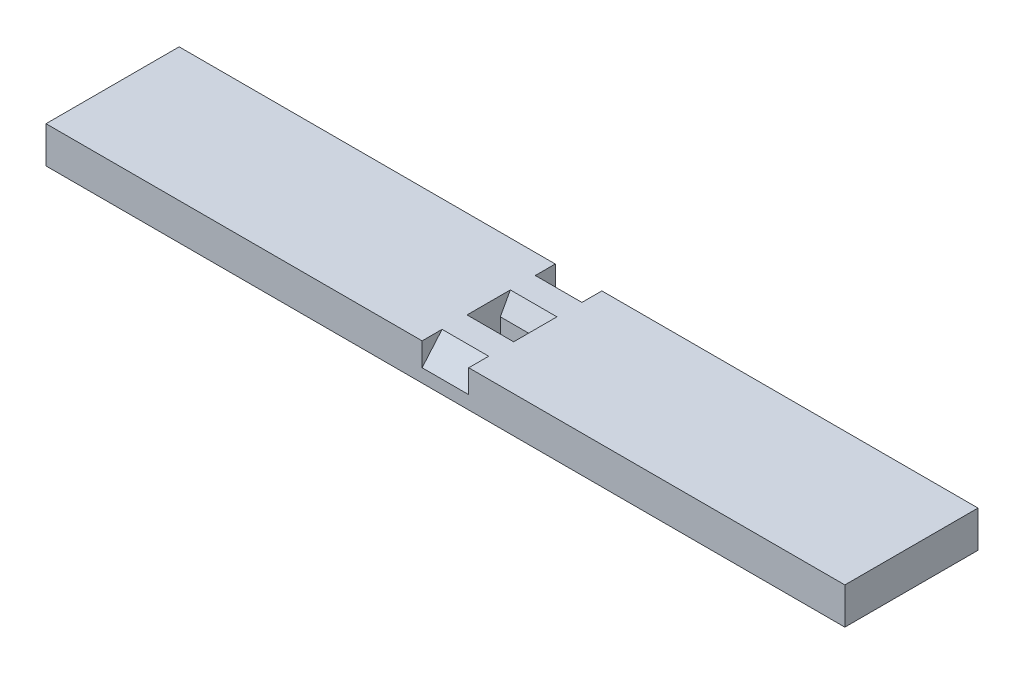
SolidWorks part; units mm, degrees
ref_plane "Front Plane" through (0, 0, 0) normal (0, 0, 1) x (1, 0, 0)
ref_plane "Top Plane" through (0, 0, 0) normal (0, 1, 0) x (1, 0, 0)
ref_plane "Right Plane" through (0, 0, 0) normal (1, 0, 0) x (0, 0, -1)
sketch "Sketch1" plane through (0, 0, 0) normal (0, 1, 0) x (1, 0, 0)
  line L1 (0, 0) -> (120, 0)
  line L2 (0, 0) -> (0, 20)
  line L3 (0, 20) -> (120, 20)
  line L4 (120, 0) -> (120, 20)
  dimension "D1" = 20
  dimension "D2" = 120
extrude "Boss-Extrude1" add sketch "Sketch1" along normal blind 5.5
sketch "Sketch2" plane through (0, 5.5, 0) normal (0, 1, 0) x (1, 0, 0)
  line L0 (60, 20) -> (60, 0) construction
  line L1 (120, 20) -> (0, 20) construction
  line L2 (0, 0) -> (120, 0) construction
  line L4 (56.5, 8.25) -> (63.5, 8.25)
  line L5 (56.5, 8.25) -> (56.5, 11.75)
  line L6 (56.5, 11.75) -> (63.5, 11.75)
  line L7 (63.5, 8.25) -> (63.5, 11.75)
  line L8 (56.5, 8.25) -> (63.5, 11.75) construction
  line L9 (56.5, 11.75) -> (63.5, 8.25) construction
  point P6 (60, 10)
  dimension "D1" = 3.5
  dimension "D2" = 7
extrude "Cut-Extrude1" cut sketch "Sketch2" against normal blind 10
sketch "Sketch3" plane through (56.5, 0, 0) normal (1, 0, 0) x (0, 0, -1)
  line L0 (8.25, 5.5) -> (6.7479, 5.5)
  line L1 (20, 5.5) -> (0, 5.5) construction
  line L2 (6.7479, 5.5) -> (8.25, 2.75)
  line L3 (8.25, 0) -> (8.25, 5.5) construction
  line L4 (8.25, 2.75) -> (8.25, 5.5)
  line L5 (11.75, 5.5) -> (13.25, 5.5)
  line L6 (13.25, 5.5) -> (11.75, 2.75)
  line L7 (11.75, 0) -> (11.75, 5.5) construction
  line L8 (11.75, 2.75) -> (11.75, 5.5)
  line L9 (3, 5.5) -> (0, 2)
  line L11 (0, 2) -> (0, 5.5)
  line L12 (0, 5.5) -> (3, 5.5)
  line L13 (17, 5.5) -> (20, 2)
  line L15 (20, 2) -> (20, 5.5)
  line L16 (20, 5.5) -> (17, 5.5)
  dimension "D1" = 1.5021
  dimension "D2" = 1.5
  dimension "D3" = 3
  dimension "D4" = 3
  dimension "D5" = 3.5
  dimension "D6" = 3.5
extrude "Cut-Extrude2" cut sketch "Sketch3" along normal up to surface (7 mm away) up to face at (63.5, 2.75, -10)
